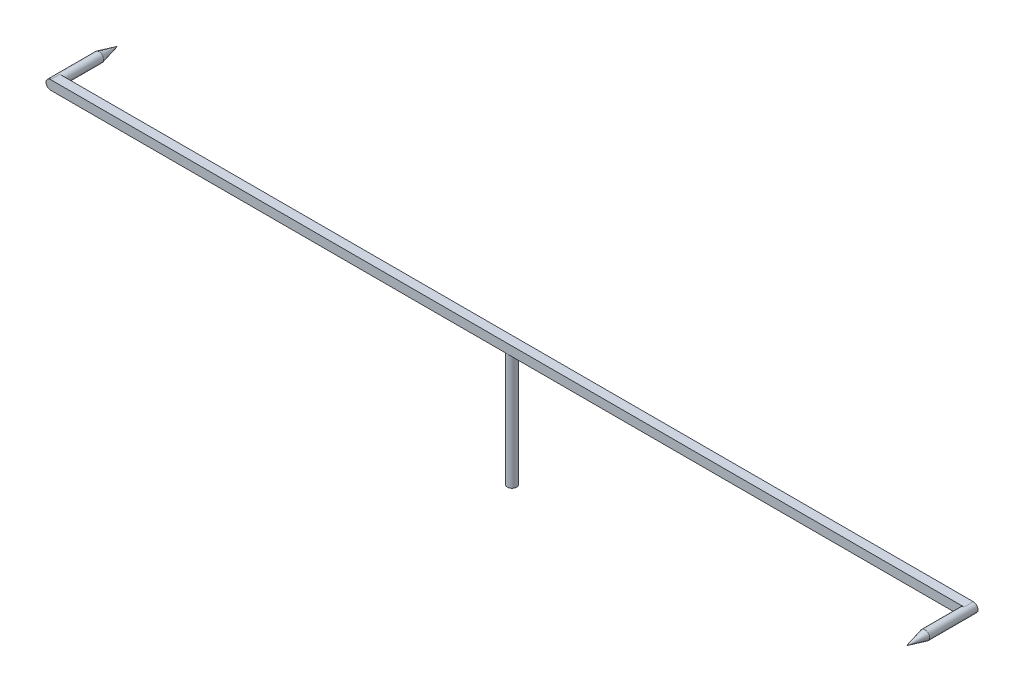
SolidWorks part; units mm, degrees
ref_plane "前视基准面" through (0, 0, 0) normal (0, 0, 1) x (1, 0, 0)
ref_plane "上视基准面" through (0, 0, 0) normal (0, 1, 0) x (1, 0, 0)
ref_plane "右视基准面" through (0, 0, 0) normal (1, 0, 0) x (0, 0, -1)
sketch "草图1" plane through (0, 0, 0) normal (0, 1, 0) x (1, 0, 0)
  circle A0 centre (0, 0) radius 0.4
  dimension "D1" = 0.8
extrude "凸台-拉伸1" add sketch "草图1" along normal blind 10
sketch "草图2" plane through (0, 10, 0) normal (0, 1, 0) x (1, 0, 0)
  line L1 (-40, 0.4) -> (40, 0.4)
  line L2 (-40, 0.4) -> (-40, -0.4)
  line L3 (-40, -0.4) -> (40, -0.4)
  line L4 (40, 0.4) -> (40, -0.4)
  circle A0 centre (0, 0) radius 0.4 construction
  dimension "D1" = 40
  dimension "D2" = 40
extrude "凸台-拉伸2" add sketch "草图2" along normal blind 0.8
fillet "圆角1" radius 0.4 4 edges at (40, 10, 0) (40, 10.8, 0) (-40, 10, 0) (-40, 10.8, 0)
sketch "草图3" plane through (0, 0, 0.4) normal (0, 0, 1) x (1, 0, 0)
  circle A0 centre (39.6, 10.4) radius 0.4
  dimension "D1" = 0.8
extrude "凸台-拉伸3" add sketch "草图3" along normal blind 3.4
sketch "草图4" plane through (0, 0, -0.4) normal (0, 0, -1) x (-1, 0, 0)
  circle A0 centre (39.6, 10.4) radius 0.4
  dimension "D1" = 0.8
extrude "凸台-拉伸4" add sketch "草图4" along normal blind 3.4
ref_plane "基准面1" through (0, 10.4, 0) normal (0, 1, 0) x (1, 0, 0)
sketch "草图5" plane through (0, 10.4, 0) normal (0, 1, 0) x (1, 0, 0)
  line L0 (39.6, -3.8) -> (39.6, -5.4)
  line L1 (39.2, -3.8) -> (40, -3.8) construction
  line L2 (40, -3.8) -> (39.6, -5.4)
  line L3 (39.6, -3.8) -> (40, -3.8)
  dimension "D1" = 1.6
revolve "旋转1" add sketch "草图5" angle 360 about L0
sketch "草图6" plane through (0, 10.4, 0) normal (0, 1, 0) x (1, 0, 0)
  line L0 (-39.6, 3.8) -> (-39.6, 5.4)
  line L1 (-39.2, 3.8) -> (-40, 3.8) construction
  line L2 (-39.6, 5.4) -> (-40, 3.8)
  line L3 (-40, 3.8) -> (-39.6, 3.8)
  dimension "D1" = 1.6
revolve "旋转2" add sketch "草图6" angle 360 about L0
